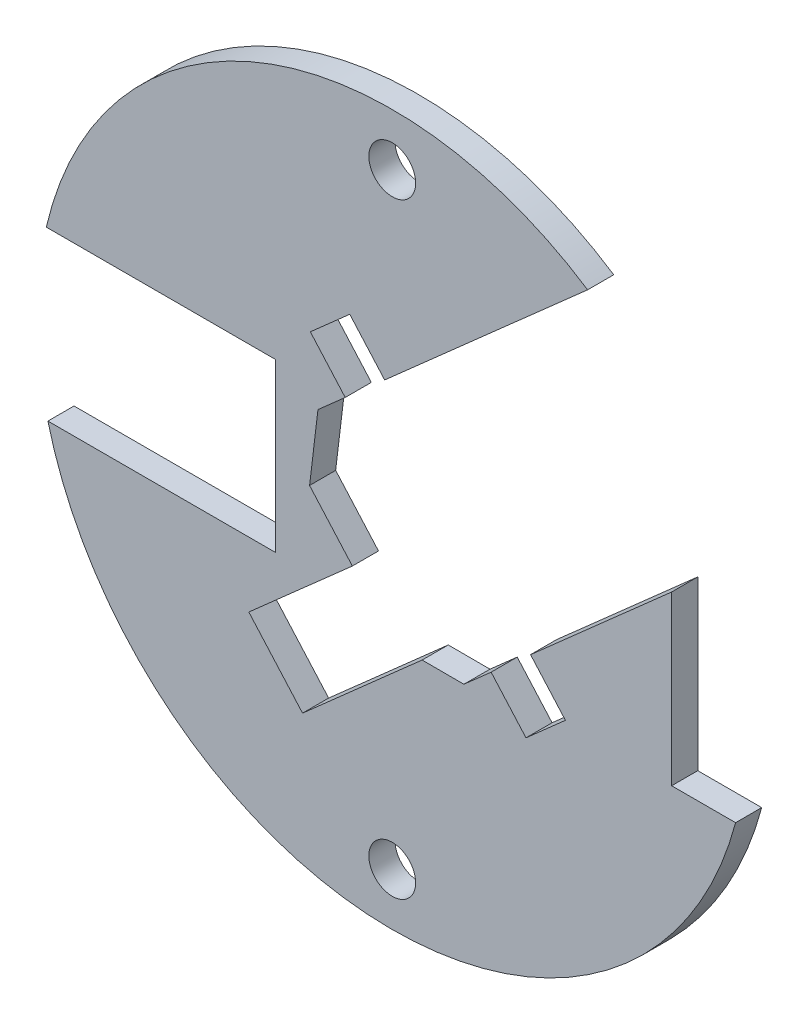
SolidWorks part; units mm, degrees
ref_plane "Front Plane" through (0, 0, 0) normal (0, 0, 1) x (1, 0, 0)
ref_plane "Top Plane" through (0, 0, 0) normal (0, 1, 0) x (1, 0, 0)
ref_plane "Right Plane" through (0, 0, 0) normal (1, 0, 0) x (0, 0, -1)
sketch "Sketch1" plane through (0, 0, 0) normal (0, 0, 1) x (1, 0, 0)
  line L0 (-21.141, 18.2245) -> (20.1141, 18.2245) construction
  line L1 (-4.8006, 1.8415) -> (-4.8006, -3.0861)
  line L2 (-4.8006, -3.0861) -> (-8.9662, -3.0861)
  line L3 (-8.9662, -3.0861) -> (-8.9662, -5.3514)
  line L4 (-8.9662, -5.3514) -> (-6.5786, -5.3514)
  line L5 (-4.9806, 7.3918) -> (-2.5835, 9.5123)
  line L6 (-2.5835, 9.5123) -> (-0.463, 7.1152)
  line L7 (-4.9806, 7.3918) -> (-2.8601, 4.9947)
  line L8 (3.2088, 10.3632) -> (-4.5153, 3.5306)
  line L9 (12.0777, 0.3371) -> (4.3536, -6.4955)
  line L10 (-4.5153, 3.5306) -> (-5.0276, -0.7207)
  line L11 (-5.0276, -0.7207) -> (0.0716, -6.4852)
  line L12 (0.0716, -6.4852) -> (4.3536, -6.4955)
  line L13 (-2.478, -3.6029) -> (7.6432, 5.3502) construction
  line L14 (3.2088, 10.3632) -> (12.0777, 0.3371)
  line L15 (3.2088, 10.3632) -> (11.8761, 18.0302)
  line L16 (-9.2588, -8.622) -> (-4.7522, -4.6355) construction
  line L17 (-9.2588, -8.622) -> (-5.994, -12.3128) construction
  line L18 (-4.7522, -4.6355) -> (-1.4874, -8.3263) construction
  line L19 (-5.994, -12.3128) -> (-1.4874, -8.3263) construction
  line L20 (12.0777, 0.3371) -> (20.228, 7.5468)
  line L21 (-6.5786, -5.3514) -> (-6.5786, -5.8039)
  line L22 (-6.5786, -5.8039) -> (-14.0208, -5.8039)
  line L23 (-14.0208, -5.8039) -> (-14.0208, 4.5593)
  line L24 (-14.0208, 4.5593) -> (-6.5786, 4.5593)
  line L25 (-6.5786, 4.5593) -> (-6.5786, 3.9924)
  line L26 (-6.5786, 3.9924) -> (-8.9662, 3.9924)
  line L27 (-8.9662, 3.9924) -> (-8.9662, 1.8415)
  line L28 (-8.9662, 1.8415) -> (-4.8006, 1.8415)
  line L29 (8.4059, -2.9109) -> (10.5264, -5.308)
  line L30 (10.5264, -5.308) -> (8.1292, -7.4285)
  line L31 (8.1292, -7.4285) -> (6.0088, -5.0313)
  line L32 (-4.7522, -4.6355) -> (-2.9639, -3.0536) construction
  line L33 (-1.4874, -8.3263) -> (0.5926, -6.4864) construction
  line L34 (-5.4555, -12.9216) -> (-0.9489, -8.9351)
  line L35 (-8.7203, -9.2308) -> (-4.2137, -5.2443)
  line L36 (-8.7203, -9.2308) -> (-5.4555, -12.9216)
  line L37 (-0.9489, -8.9351) -> (1.816, -6.4894)
  line L38 (-4.2137, -5.2443) -> (-2.4254, -3.6624)
  arc A0 (-15.2315, -0.5079) -> (3.302, 14.878) centre (0, 0) ccw construction
  circle A1 centre (0, 0) radius 21.59 construction
  circle A2 centre (0, 0) radius 21.59
  circle A3 centre (0, -18.415) radius 1.4224 construction
  circle A4 centre (0, 18.415) radius 1.4224 construction
  circle A5 centre (0, -18.415) radius 1.4224
  circle A6 centre (0, 18.415) radius 1.4224
  circle A7 centre (0, 0) radius 15.24
  dimension "D3" = 30.48
  dimension "D1" = 33.4645
  dimension "D2" = 20.0406
  dimension "D4" = 4.9276
  dimension "D5" = 2.7178
  dimension "D6" = 8.7122
  dimension "D7" = 7.8613
  dimension "D8" = 2.7178
  dimension "D9" = 3.2004
  dimension "D10" = 13.3858
  dimension "D11" = 3.1623
  dimension "D12" = 10.3124
  dimension "D13" = 8.6106
  dimension "D14" = 7.6962
  dimension "D15" = 6.0168
  dimension "D16" = 2.3876
  dimension "D17" = 4.9276
  dimension "D18" = 22.86
  dimension "D19" = 7.4422
  dimension "D20" = 5.0546
  dimension "D21" = 13.6652
  dimension "D22" = 29.2608
  dimension "D23" = 0.8128
extrude "Boss-Extrude1" add sketch "Sketch1" along normal blind 1.5875 contours L15 A7 L20 L9 L29 L30 L31 L12 L33 L19 L17 L16 L32 L11 L1 L2 L3 L4 L21 L22 L23 L24 L25 L26 L27 L28 L10 L8 L7 L5 L6 | L28 L27 L26 L25 L24 L23 L22 L21 L4 L3 L2 L1 L11 L10 | A7 L15 A2 L20 A6 A5 region at (-6.8834, 2.2726, 0) region at (-10.1343, -0.6067, 0) region at (-13.5004, -8.3055, 0)
sketch "Sketch2" plane through (0, 0, 1.5875) normal (0, 0, 1) x (1, 0, 0)
  line L0 (-5.0276, 2.3876) -> (-5.0276, -2.794)
  line L1 (-5.0276, 2.3876) -> (-10.4871, 2.3876)
  line L2 (-10.4871, 2.3876) -> (-10.4871, 3.8608)
  line L3 (-10.4871, 3.8608) -> (-7.085, 3.8608)
  line L4 (-7.085, 3.8608) -> (-7.085, 4.8768)
  line L5 (-7.085, 4.8768) -> (-14.4764, 4.8768)
  line L6 (-14.4764, 4.8768) -> (-14.4764, -5.2832)
  line L7 (-14.4764, -5.2832) -> (-7.085, -5.2832)
  line L8 (-7.085, -5.2832) -> (-7.085, -4.2672)
  line L9 (-7.085, -4.2672) -> (-10.4871, -4.2672)
  line L10 (-10.4871, -4.2672) -> (-10.4871, -2.794)
  line L11 (-10.4871, -2.794) -> (-5.0276, -2.794)
  line L12 (-5.0276, 2.3876) -> (-4.653, 2.3876)
  line L13 (-4.5153, 3.5306) -> (-5.0276, -0.7207) construction
  line L14 (-5.0276, -2.794) -> (-3.1935, -2.794)
  line L15 (-5.0276, -0.7207) -> (-2.4254, -3.6624) construction
  line L16 (-7.085, 3.8608) -> (-7.085, -4.2672)
  line L17 (-14.4764, 4.8768) -> (-21.032, 4.8768)
  line L18 (-14.4764, -5.2832) -> (-20.9336, -5.2832)
  arc A0 (11.8761, 18.0302) -> (20.228, 7.5468) centre (0, 0) ccw construction
  arc M2 (11.8761, 18.0302) -> (20.228, 7.5468) centre (0, 0) ccw
  dimension "D1" = 9.4488
  dimension "D2" = 7.3914
  dimension "D3" = 10.16
  dimension "D4" = 1.016
  dimension "D5" = 5.1816
  dimension "D6" = 5.4596
  dimension "D7" = 1.4732
  dimension "D8" = 1.143
extrude "Cut-Extrude3" cut sketch "Sketch2" against normal through all contours L10 L11 L0 L1 L2 L3 L4 L5 L6 L7 L8 L9 | L16 L3 L2 L1 | L16 L11 L10 L9 | L18 L6 L17 M2 region at (-11.0879, -0.2032, 1.5875) region at (-8.7861, 3.1242, 1.5875) region at (-8.7861, -3.5306, 1.5875) region at (-17.9346, -0.1913, 1.5875)
sketch "Sketch3" plane through (0, 0, 0) normal (0, 0, -1) x (-1, 0, 0)
  line L0 (-20.8712, -5.5245) -> (-16.9841, -5.5245)
  line L1 (-16.9841, -5.5245) -> (-20.8712, -5.5245) construction
  line L2 (-16.9841, -5.5245) -> (-16.9841, 4.6772)
  line L3 (-8.4059, -2.9109) -> (-20.228, 7.5468) construction
  line L4 (-16.9841, 5.5245) -> (-16.9841, -5.5245) construction
  line L5 (-16.9841, 4.6772) -> (-20.228, 7.5468)
  arc A0 (-20.228, 7.5468) -> (20.9336, -5.2832) centre (0, 0) ccw construction
  arc A1 (-20.228, 7.5468) -> (-20.8712, -5.5245) centre (0, 0) ccw
  arc A2 (-20.8712, -5.5245) -> (-20.8712, 5.5245) centre (0, 0) ccw construction
extrude "Cut-Extrude4" cut sketch "Sketch3" against normal through all
